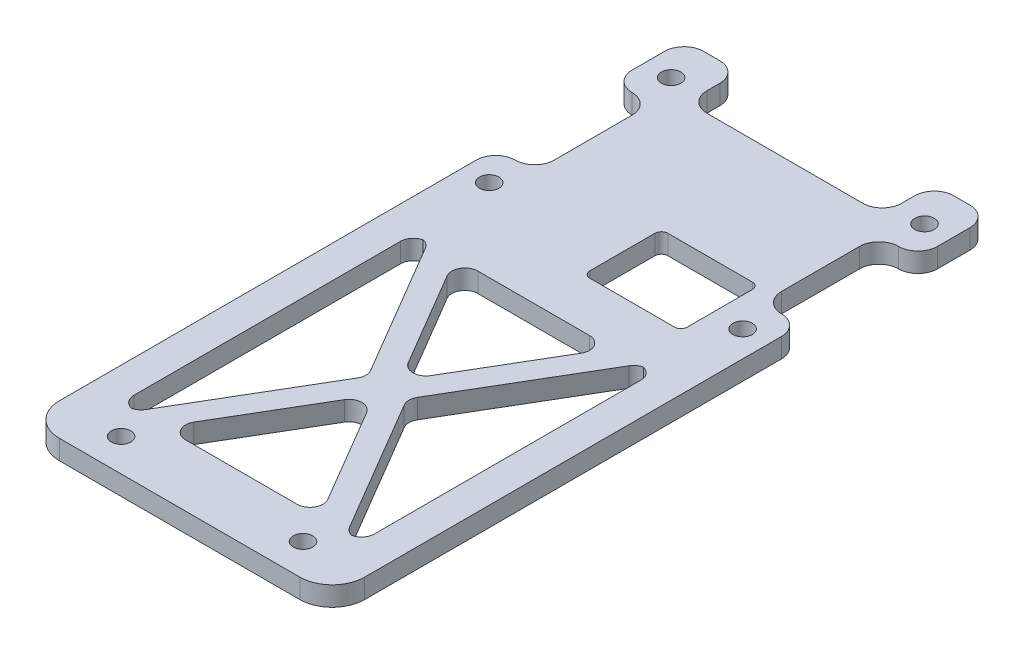
SolidWorks part; units mm, degrees
material "Thornel Mat VMA"
ref_plane "前视基准面" through (0, 0, 0) normal (0, 0, 1) x (1, 0, 0)
ref_plane "上视基准面" through (0, 0, 0) normal (0, 1, 0) x (1, 0, 0)
ref_plane "右视基准面" through (0, 0, 0) normal (1, 0, 0) x (0, 0, -1)
other "Configuration Table"
sketch "草图1" plane through (0, 0, 0) normal (0, 1, 0) x (1, 0, 0)
  line L0 (0, 0) -> (0, 40.9092) construction
  line L1 (-23.5, -20) -> (23.5, -20)
  line L2 (-23.5, -20) -> (-23.5, 20)
  line L3 (-23.5, 20) -> (23.5, 20)
  line L4 (23.5, -20) -> (23.5, 20)
  line L5 (-23.5, -20) -> (23.5, 20) construction
  line L6 (-23.5, 20) -> (23.5, -20) construction
  line L7 (0, 0) -> (66.2179, 0) construction
  line L16 (0, 0) -> (0, -21.1131) construction
  line L17 (-15, -7) -> (15, -7)
  line L18 (15, -7) -> (15, -19)
  line L19 (15, -19) -> (-15, -19)
  line L20 (-15, -7) -> (-15, -19)
  line L21 (-23.5, -20) -> (-23.5, -86.16)
  line L22 (-23.5, -86.16) -> (23.5, -86.16)
  line L23 (23.5, -86.16) -> (23.5, -20)
  line L24 (0, -7) -> (0, -19)
  circle A0 centre (19.5, 14) radius 1.5
  circle A1 centre (19.5, -14) radius 1.5
  circle A2 centre (-19.5, -14) radius 1.5
  circle A3 centre (-19.5, 14) radius 1.5
  point P0 (0, 0)
  point P23 (0, -19)
  point P24 (0, -7)
  dimension "D3" = 3
  dimension "D4" = 39
  dimension "D5" = 28
  dimension "D1" = 47
  dimension "D2" = 40
  dimension "D6" = 30
  dimension "D7" = 12
  dimension "D8" = 7
  dimension "D9" = 86.16
extrude "凸台-拉伸1" add sketch "草图1" along normal blind 3 contours L1 L4 L3 L2 A1 A0 L20 L17 L18 L19 A2 A3 | L22 L23 L1 L21 | L24 L17 L20 L19 region at (0, 0, -3.1373) region at (0, 0, 53.08) region at (-7.5, 0, 13)
sketch "草图4" plane through (0, 3, 0) normal (0, 1, 0) x (1, 0, 0)
  line L0 (0, 0) -> (0, -81.16) construction
  line L2 (-23.5, -81.16) -> (23.5, -81.16)
  line L3 (-23.5, -86.16) -> (-23.5, 20) construction
  line L4 (23.5, -86.16) -> (23.5, 20) construction
  line L5 (23.5, -81.16) -> (23.5, -86.16)
  line L6 (23.5, -86.16) -> (-23.5, -86.16)
  line L7 (-23.5, -86.16) -> (-23.5, -81.16)
  circle A8 centre (-14, -76.16) radius 1.5
  circle A9 centre (14, -76.16) radius 1.5
  dimension "D1" = 3
  dimension "D2" = 28
  dimension "D3" = 5
  dimension "D7" = 5
extrude "切除-拉伸2" cut sketch "草图4" against normal blind 4
sketch "草图7" plane through (0, 3, 0) normal (0, 1, 0) x (1, 0, 0)
  line L0 (0, 0) -> (0, 35.6954) construction
  line L1 (0, 0) -> (61.3613, 0) construction
  line L9 (-15, 12) -> (15, 12)
  line L10 (15, 12) -> (15, 20)
  line L11 (-23.5, 20) -> (23.5, 20) construction
  line L12 (15, 20) -> (-15, 20)
  line L13 (17.5, -9) -> (17.5, 9)
  line L14 (17.5, 9) -> (23.5, 9)
  line L15 (23.5, -81.16) -> (23.5, 20) construction
  line L16 (23.5, 9) -> (23.5, -9)
  line L17 (-23.5, 9) -> (-23.5, -9)
  line L18 (-17.5, 9) -> (-23.5, 9)
  line L19 (-17.5, -9) -> (-17.5, 9)
  line L20 (-15, 12) -> (-15, 20)
  line L21 (-17.5, -9) -> (-23.5, -9)
  line L22 (17.5, -9) -> (23.5, -9)
  point P21 (0, 20)
  point P22 (0, 12)
  point P23 (-17.5, 0)
  point P24 (-23.5, 0)
  point P26 (23.5, 0)
  point P27 (17.5, 0)
  dimension "D1" = 15
  dimension "D2" = 8
  dimension "D3" = 9
  dimension "D4" = 6
extrude "切除-拉伸3" cut sketch "草图7" against normal blind 10
fillet "圆角2" radius 3 2 edges at (23.5, 1.5, -20) (-23.5, 1.5, -20)
fillet "圆角3" radius 1 4 edges at (0, 1.5, 19) (15, 1.5, 19) (15, 1.5, 7) (0, 1.5, 7)
sketch "草图9" plane through (0, 3, 0) normal (0, 1, 0) x (1, 0, 0)
  line L0 (0, -81.16) -> (0, 21.7085) construction
  line L1 (23.5, -81.16) -> (-23.5, -81.16) construction
  line L2 (0, -49.16) -> (69.6905, -49.16) construction
  line L3 (12.0804, -26.66) -> (0, -47.16)
  line L4 (-18.5, -71.66) -> (18.5, -71.66)
  line L5 (-18.5, -71.66) -> (-18.5, -26.66)
  line L6 (-18.5, -26.66) -> (18.5, -26.66)
  line L7 (18.5, -71.66) -> (18.5, -26.66)
  line L8 (-18.5, -71.66) -> (18.5, -26.66) construction
  line L9 (-18.5, -26.66) -> (18.5, -71.66) construction
  line L10 (16.2589, -26.66) -> (3, -49.16)
  line L11 (-16.2589, -26.66) -> (-3, -49.16)
  line L12 (-12.0804, -26.66) -> (0, -47.16)
  line L13 (16.2589, -71.66) -> (3, -49.16)
  line L14 (12.0804, -71.66) -> (0, -51.16)
  line L15 (-12.0804, -71.66) -> (0, -51.16)
  line L16 (-16.2589, -71.66) -> (-3, -49.16)
  dimension "D1" = 37
  dimension "D2" = 45
  dimension "D3" = 32
  dimension "D4" = 2
  dimension "D5" = 3
  dimension "D6" = 3.6
extrude "切除-拉伸4" cut sketch "草图9" against normal blind 10 contours L4 L16 L11 L6 L5 | L6 L12 L3 | L13 L4 L7 L6 L10 | L15 L4 L14 region at (0, 3, 33.4933) region at (13.239, 3, 49.16) region at (-13.239, 3, 49.16) region at (0, 3, 64.8267)
fillet "圆角4" radius 2 16 edges at (-16.2589, 1.5, 71.66) (-18.5, 1.5, 71.66) (-12.0804, 1.5, 71.66) (12.0804, 1.5, 71.66) (18.5, 1.5, 71.66) (16.2589, 1.5, 71.66) (3, 1.5, 49.16) (0, 1.5, 51.16) (-3, 1.5, 49.16) (0, 1.5, 47.16) (18.5, 1.5, 26.66) (16.2589, 1.5, 26.66) (12.0804, 1.5, 26.66) (-12.0804, 1.5, 26.66) (-16.2589, 1.5, 26.66) (-18.5, 1.5, 26.66)
fillet "圆角5" radius 5 2 edges at (23.5, 1.5, 81.16) (-23.5, 1.5, 81.16)
fillet "圆角6" radius 3 8 edges at (-17.5, 1.5, 9) (17.5, 1.5, 9) (17.5, 1.5, -9) (-15, 1.5, -20) (15, 1.5, -20) (15, 1.5, -12) (-15, 1.5, -12) (-17.5, 1.5, -9)
fillet "圆角7" radius 3 4 edges at (-23.5, 1.5, 9) (23.5, 1.5, 9) (23.5, 1.5, -9) (-23.5, 1.5, -9)
